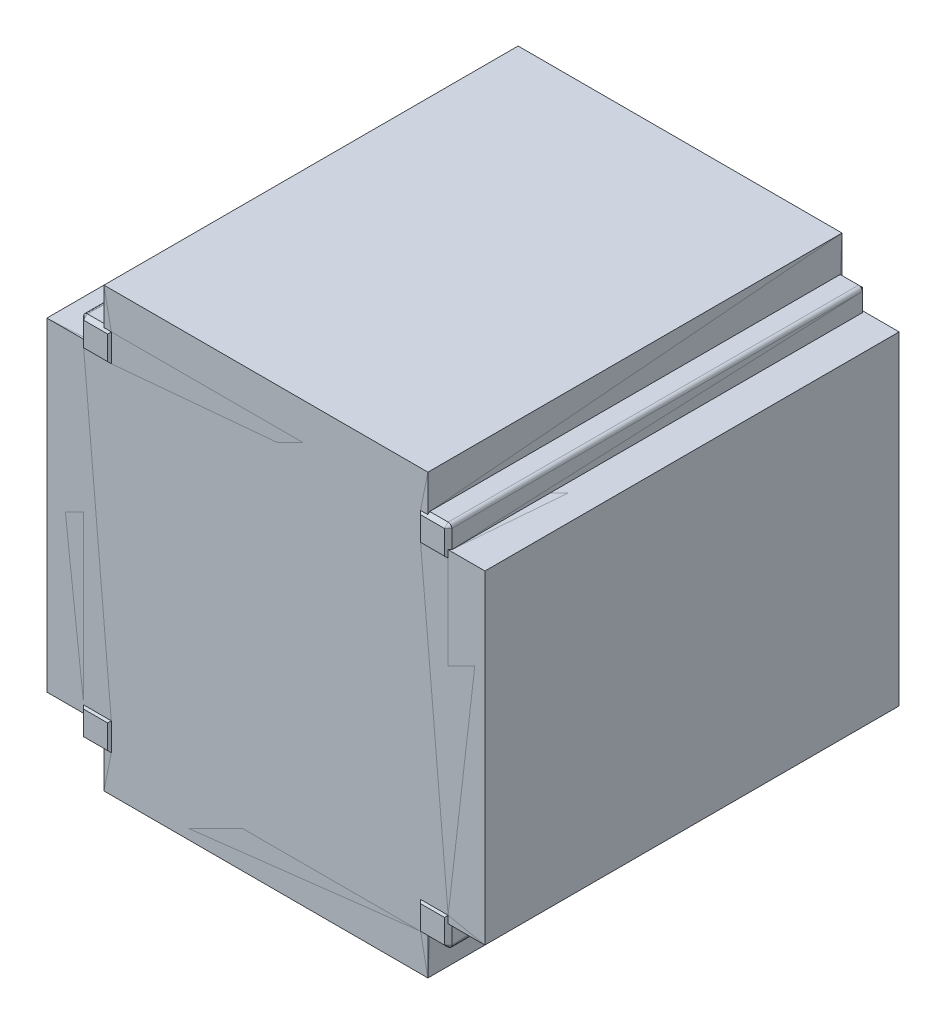
SolidWorks part; units mm, degrees
ref_plane "Front Plane" through (0, 0, 0) normal (0, 0, 1) x (1, 0, 0)
ref_plane "Top Plane" through (0, 0, 0) normal (0, 1, 0) x (1, 0, 0)
ref_plane "Right Plane" through (0, 0, 0) normal (1, 0, 0) x (0, 0, -1)
sketch "Sketch1" plane through (0, 0, 0) normal (0, 0, 1) x (1, 0, 0)
  line L1 (-50, -50) -> (50, -50) construction
  line L2 (-50, -50) -> (-50, 50) construction
  line L3 (-50, 50) -> (50, 50) construction
  line L4 (50, -50) -> (50, 50) construction
  line L5 (-50, -50) -> (50, 50) construction
  line L6 (-50, 50) -> (50, -50) construction
  line L23 (-50, 50) -> (-41.5, 50)
  line L24 (-50, 50) -> (-50, 41.5)
  line L25 (-50, 41.5) -> (-41.5, 41.5)
  line L26 (-41.5, 50) -> (-41.5, 41.5)
  line L27 (50, 50) -> (41.5, 50)
  line L28 (50, 50) -> (50, 41.5)
  line L29 (50, 41.5) -> (41.5, 41.5)
  line L30 (41.5, 50) -> (41.5, 41.5)
  line L31 (50, -50) -> (41.5, -50)
  line L32 (50, -50) -> (50, -41.5)
  line L33 (50, -41.5) -> (41.5, -41.5)
  line L34 (41.5, -50) -> (41.5, -41.5)
  line L35 (-50, -50) -> (-41.5, -50)
  line L36 (-50, -50) -> (-50, -41.5)
  line L37 (-50, -41.5) -> (-41.5, -41.5)
  line L38 (-41.5, -50) -> (-41.5, -41.5)
  point P0 (0, 0)
  dimension "D1" = 100
  dimension "D2" = 100
  dimension "D3" = 8.5
extrude "Boss-Extrude1" add sketch "Sketch1" along normal blind 56.75 and the other way blind 56.75
sketch "Sketch2" plane through (0, 0, 0) normal (0, 0, 1) x (1, 0, 0)
  line L1 (-50, -50) -> (50, -50) construction
  line L2 (-50, -50) -> (-50, 50) construction
  line L3 (-50, 50) -> (50, 50) construction
  line L4 (50, -50) -> (50, 50) construction
  line L5 (-50, -50) -> (50, 50) construction
  line L6 (-50, 50) -> (50, -50) construction
  line L21 (-65.5532, 0) -> (65.5532, 0) construction
  line L28 (-44, 50) -> (-44, 59.5)
  line L29 (-44, 59.5) -> (44, 59.5)
  line L30 (44, 59.5) -> (44, 50)
  line L31 (44, 50) -> (50, 50)
  line L32 (50, 50) -> (50, 44)
  line L33 (50, 44) -> (59.5, 44)
  line L34 (59.5, 44) -> (59.5, -44)
  line L35 (59.5, -44) -> (50, -44)
  line L36 (50, -44) -> (50, -50)
  line L37 (50, -50) -> (44, -50)
  line L38 (44, -50) -> (44, -59.5)
  line L39 (44, -59.5) -> (-44, -59.5)
  line L40 (-44, -59.5) -> (-44, -50)
  line L41 (-44, -50) -> (-50, -50)
  line L42 (-50, -50) -> (-50, -44)
  line L43 (-50, -44) -> (-59.5, -44)
  line L44 (-59.5, -44) -> (-59.5, 44)
  line L45 (-59.5, 44) -> (-50, 44)
  line L46 (-50, 44) -> (-50, 50)
  line L47 (-50, 50) -> (-44, 50)
  point P0 (0, 0)
  point P21 (-59.5, 0)
  point P27 (59.5, 0)
  point P28 (0, 59.5)
  point P30 (0, -59.5)
  dimension "D1" = 88
  dimension "D2" = 88
  dimension "D3" = 119
  dimension "D4" = 119
extrude "Boss-Extrude2" add sketch "Sketch2" along normal blind 56.25 and the other way blind 56.25
fillet "Fillet1" radius 1 4 edges at (-50, -50, 0) (50, 50, 0) (50, -50, 0) (-50, 50, 0)
chamfer "Chamfer2" distance 1 angle 45 40 edges at (-45.75, -41.5, 56.75) (-41.5, -45.75, 56.75) (-45.25, -50, 56.75) (-49.7071, -49.7071, 56.75) (-50, -45.25, 56.75) (41.5, -45.75, 56.75) (45.75, -41.5, 56.75) (45.75, 41.5, 56.75) (41.5, 45.75, 56.75) (45.25, 50, 56.75) (49.7071, 49.7071, 56.75) (50, 45.25, 56.75) (-41.5, 45.75, 56.75) (-45.75, 41.5, 56.75) (41.5, 45.75, -56.75) (45.75, 41.5, -56.75) (50, 45.25, -56.75) (49.7071, 49.7071, -56.75) (45.25, 50, -56.75) (-45.75, 41.5, -56.75) (-41.5, 45.75, -56.75) (-41.5, -45.75, -56.75) (-45.75, -41.5, -56.75) (-50, -45.25, -56.75) (-49.7071, -49.7071, -56.75) (-45.25, -50, -56.75) (45.75, -41.5, -56.75) (41.5, -45.75, -56.75) (45.25, -50, 56.75) (50, -45.25, 56.75) (-45.25, 50, 56.75) (-50, 45.25, 56.75) (-45.25, 50, -56.75) (-50, 45.25, -56.75) (45.25, -50, -56.75) (50, -45.25, -56.75) (49.7071, -49.7071, 56.75) (-49.7071, 49.7071, 56.75) (-49.7071, 49.7071, -56.75) (49.7071, -49.7071, -56.75)
surface "Surface-Offset1" parameters "D1"=0
equation "\"D1@Boss-Extrude1\"=113.5/2mm"
equation "\"D2@Boss-Extrude1\"=113.5/2"
